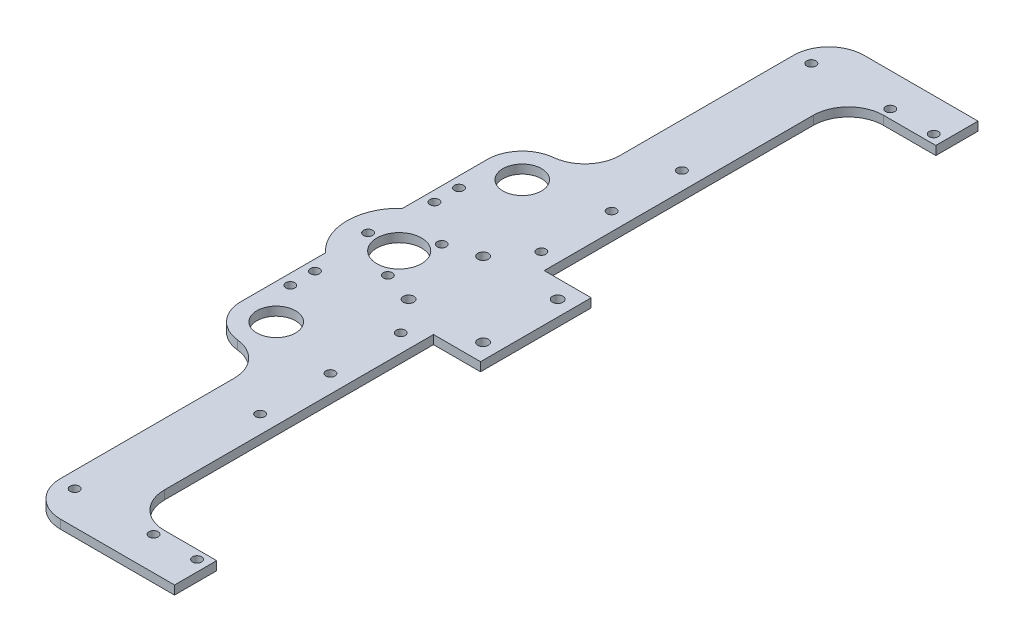
SolidWorks part; units mm, degrees
ref_plane "Front Plane" through (0, 0, 0) normal (0, 0, 1) x (1, 0, 0)
ref_plane "Top Plane" through (0, 0, 0) normal (0, 1, 0) x (1, 0, 0)
ref_plane "Right Plane" through (0, 0, 0) normal (1, 0, 0) x (0, 0, -1)
sketch "Sketch1" plane through (0, 0, 0) normal (0, 1, 0) x (1, 0, 0)
  line L0 (-67.9713, -52.7283) -> (-67.9713, -82.5864)
  line L6 (-67.9713, 4.9919) -> (-67.9713, -24.8662)
  line L17 (8.6823, 106.3552) -> (-32.5284, 106.3552)
  line L20 (-32.5284, -183.9497) -> (7.3984, -183.9497)
  line L24 (-10.2035, 91.1152) -> (8.6823, 91.1152)
  line L26 (7.3984, -183.9497) -> (8.6823, -183.9497)
  line L28 (-10.2035, -168.7097) -> (8.6823, -168.7097)
  line L30 (8.6823, -168.7097) -> (8.6823, -183.9497)
  line L31 (-45.2284, -108.5097) -> (-45.2284, -171.2497)
  line L32 (8.6823, 106.3552) -> (8.6823, 91.1152)
  line L33 (-45.2284, 93.6552) -> (-45.2284, 30.9152)
  line L34 (-22.9035, -156.0097) -> (-22.9035, -58.7973)
  line L35 (-22.9035, -38.7973) -> (-5.9035, -38.7973) construction
  line L40 (-5.9035, -38.7973) -> (-5.9035, -18.7973)
  line L41 (-5.9035, -38.7973) -> (-5.9035, -58.7973)
  line L42 (-5.9035, -18.7973) -> (-22.9035, -18.7973)
  line L43 (-5.9035, -58.7973) -> (-22.9035, -58.7973)
  line L44 (-22.9035, -18.7973) -> (-22.9035, 78.4152)
  arc A0 (-67.9713, -82.5864) -> (-56.6084, -95.8785) centre (-55.2885, -83.2473) ccw
  arc A1 (-45.2284, -108.5097) -> (-56.6084, -95.8785) centre (-57.9284, -108.5097) ccw
  arc A4 (-56.6084, 18.284) -> (-45.2284, 30.9152) centre (-57.9284, 30.9152) ccw
  arc A5 (-56.6084, 18.284) -> (-67.9713, 4.9919) centre (-55.2885, 5.6527) ccw
  arc A6 (-67.9713, -24.8662) -> (-67.9713, -52.7283) centre (-55.2885, -38.7973) ccw
  arc A22 (-45.2284, 93.6552) -> (-32.5284, 106.3552) centre (-32.5284, 93.6552) cw
  arc A23 (-45.2284, -171.2497) -> (-32.5284, -183.9497) centre (-32.5284, -171.2497) ccw
  arc A24 (-22.9035, 78.4152) -> (-10.2035, 91.1152) centre (-10.2035, 78.4152) cw
  arc A25 (-22.9035, -156.0097) -> (-10.2035, -168.7097) centre (-10.2035, -156.0097) ccw
  circle A30 centre (-55.2885, -83.2473) radius 6.985 construction
  circle A31 centre (-64.1613, -69.2773) radius 1.65 construction
  circle A32 centre (-64.1613, -60.3873) radius 1.65 construction
  circle A33 centre (-55.2885, -38.7973) radius 8.0645 construction
  circle A34 centre (-49.6688, -29.0636) radius 1.65 construction
  circle A35 centre (-49.6688, -48.531) radius 1.65 construction
  circle A36 centre (-66.528, -38.7973) radius 1.65 construction
  circle A37 centre (-64.1613, -17.2073) radius 1.65 construction
  circle A38 centre (-64.1613, -8.3173) radius 1.65 construction
  circle A39 centre (-55.2885, 5.6527) radius 6.985 construction
  circle A40 centre (-55.2885, -83.2473) radius 6.985
  circle A41 centre (-64.1613, -69.2773) radius 1.65
  circle A42 centre (-64.1613, -60.3873) radius 1.65
  circle A43 centre (-55.2885, -38.7973) radius 8.0645
  circle A44 centre (-49.6688, -29.0636) radius 1.65
  circle A45 centre (-49.6688, -48.531) radius 1.65
  circle A46 centre (-66.528, -38.7973) radius 1.65
  circle A47 centre (-64.1613, -17.2073) radius 1.65
  circle A48 centre (-64.1613, -8.3173) radius 1.65
  circle A49 centre (-55.2885, 5.6527) radius 6.985
  circle A50 centre (-29.342, 37.4027) radius 1.65 construction
  circle A51 centre (-29.342, 12.0027) radius 1.65 construction
  circle A52 centre (-29.342, -13.3973) radius 1.65 construction
  circle A54 centre (-29.342, -64.1973) radius 1.65 construction
  circle A55 centre (-29.342, -89.5973) radius 1.65 construction
  circle A56 centre (-29.342, -114.9973) radius 1.65 construction
  circle A57 centre (-29.342, 37.4027) radius 1.65
  circle A58 centre (-29.342, 12.0027) radius 1.65
  circle A59 centre (-29.342, -13.3973) radius 1.65
  circle A61 centre (-29.342, -64.1973) radius 1.65
  circle A62 centre (-29.342, -89.5973) radius 1.65
  circle A63 centre (-29.342, -114.9973) radius 1.65
  point P58 (-45.2284, 106.3552)
  dimension "D3" = 63.9708
  dimension "D5" = 15.24
  dimension "D6" = 10.0601
  dimension "D7" = 32.385
  dimension "D8" = 62.74
  dimension "D44" = 12.7
  dimension "D46" = 12.7
  dimension "D47" = 12.7
  dimension "D1" = 17
  dimension "D2" = 20
extrude "Boss-Extrude1" add sketch "Sketch1" along normal blind 3.175 contours A25 A24 L24 L32 A22 A4 A5 L6 A6 L0 A0 A1 A23 L20 L26 L30 L28 A63 A62 A61 A59 A58 A57 A49 A48 A47 A46 region at (-34.9114, 0, 38.7973)
sketch "Sketch4" plane through (0, 3.175, 0) normal (0, 1, 0) x (1, 0, 0)
  circle A0 centre (4.754, 94.2902) radius 1.65
  circle A1 centre (-10.971, 94.2902) radius 1.65
  circle A2 centre (-39.471, 94.2902) radius 1.65
  circle A3 centre (-39.471, -171.8847) radius 1.65
  circle A4 centre (-10.971, -171.8847) radius 1.65
  circle A5 centre (4.754, -171.8847) radius 1.65
  dimension "D1" = 3.3
extrude "Cut-Extrude1" cut sketch "Sketch4" against normal through all
sketch "Sketch5" plane through (0, 3.175, 0) normal (0, 1, 0) x (1, 0, 0)
  circle A1 centre (-11.5006, -25.3269) radius 1.8986
  circle A2 centre (-38.4414, -25.3269) radius 1.8986
  circle A5 centre (-38.4414, -52.2677) radius 1.8986
  circle A6 centre (-11.5006, -52.2677) radius 1.8986
  point P9 (-38.4414, -52.2677)
  point P17 (-11.5006, -52.2677)
  point P18 (-11.5006, -25.3269)
  point P19 (-38.4414, -52.2677)
  dimension "D1" = 3.7973
extrude "Cut-Extrude2" cut sketch "Sketch5" against normal through all
